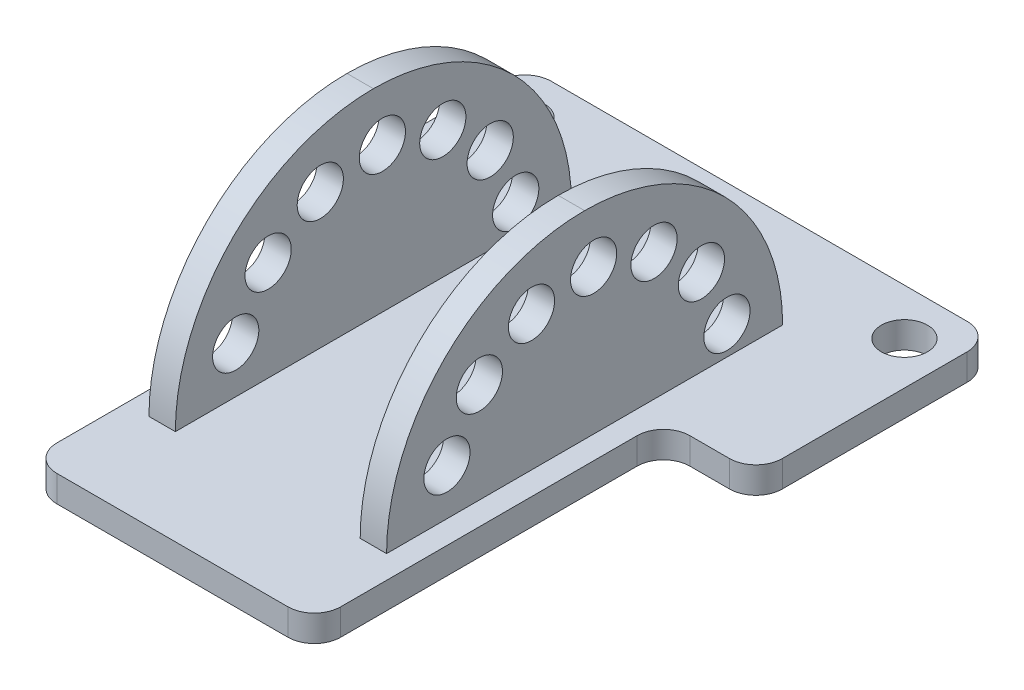
SolidWorks part; units mm, degrees
ref_plane "Front Plane" through (0, 0, 0) normal (0, 0, 1) x (1, 0, 0)
ref_plane "Top Plane" through (0, 0, 0) normal (0, 1, 0) x (1, 0, 0)
ref_plane "Right Plane" through (0, 0, 0) normal (1, 0, 0) x (0, 0, -1)
sketch "Sketch1" plane through (0, 0, 0) normal (0, 1, 0) x (1, 0, 0)
  line L1 (-17.75, 22.225) -> (17.75, 22.225)
  line L2 (-17.75, 22.225) -> (-17.75, -22.225)
  line L3 (-17.75, -22.225) -> (17.75, -22.225)
  line L4 (17.75, 22.225) -> (17.75, -22.225)
  line L5 (-17.75, 22.225) -> (17.75, -22.225) construction
  line L6 (-17.75, -22.225) -> (17.75, 22.225) construction
  point P0 (0, 0)
  dimension "D1" = 35.5
  dimension "D2" = 44.45
extrude "Boss-Extrude1" add sketch "Sketch1" along normal blind 2
sketch "Sketch2" plane through (0, 2, 0) normal (0, 1, 0) x (1, 0, 0)
  line L0 (17.75, 22.225) -> (-17.75, 22.225) construction
  circle A0 centre (-14.5, 18.725) radius 1.75
  circle A1 centre (14.5, 18.725) radius 1.75
  point P4 (0, 22.225)
  dimension "D3" = 3.5
  dimension "D4" = 3.5
  dimension "D1" = 14.5
  dimension "D2" = 14.5
  dimension "D5" = 3.5
  dimension "D6" = 3.5
extrude "Cut-Extrude1" cut sketch "Sketch2" against normal through all
sketch "Sketch3" plane through (0, 2, 0) normal (0, 1, 0) x (1, 0, 0)
  line L0 (-17.75, 22.225) -> (-17.75, -22.225) construction
  line L1 (-17.75, 4.225) -> (-10.75, 4.225)
  line L2 (-17.75, 4.225) -> (-17.75, -22.225)
  line L3 (-17.75, -22.225) -> (-10.75, -22.225)
  line L4 (-10.75, 4.225) -> (-10.75, -22.225)
  line L5 (-17.75, -22.225) -> (17.75, -22.225) construction
  line L6 (17.75, -22.225) -> (17.75, 22.225) construction
  line L7 (17.75, 4.225) -> (10.75, 4.225)
  line L8 (17.75, 4.225) -> (17.75, -22.225)
  line L9 (17.75, -22.225) -> (10.75, -22.225)
  line L10 (10.75, 4.225) -> (10.75, -22.225)
  line L11 (17.75, 22.225) -> (-17.75, 22.225) construction
  dimension "D1" = 7
  dimension "D2" = 7
  dimension "D3" = 18
  dimension "D4" = 18
extrude "Cut-Extrude2" cut sketch "Sketch3" against normal through all
fillet "Fillet1" radius 2 8 edges at (-10.75, 1, -4.225) (-17.75, 1, -4.225) (-10.75, 1, 22.225) (10.75, 1, 22.225) (10.75, 1, -4.225) (17.75, 1, -4.225) (17.75, 1, -22.225) (-17.75, 1, -22.225)
sketch "Sketch4" plane through (0, 2, 0) normal (0, 1, 0) x (1, 0, 0)
  line L1 (-9, 15) -> (-7, 15)
  line L2 (-9, 15) -> (-9, -15)
  line L3 (-9, -15) -> (-7, -15)
  line L4 (-7, 15) -> (-7, -15)
  dimension "D1" = 15
  dimension "D2" = 30
  dimension "D3" = 2
  dimension "D4" = 7
extrude "Boss-Extrude3" add sketch "Sketch4" along normal blind 15
fillet "Fillet2" radius 15 2 edges at (-8, 17, 15) (-8, 17, -15)
sketch "Sketch5" plane through (-9, 0, 0) normal (-1, 0, 0) x (0, 0, 1)
  line L1 (-15, 2) -> (15, 2) construction
  circle A0 centre (10.4283, 5.5) radius 1.75
  arc A1 (15, 2) -> (0, 17) centre (0, 2) ccw construction
  dimension "D3" = 3.5
  dimension "D1" = 3.5
  dimension "D2" = 11
extrude "Cut-Extrude3" cut sketch "Sketch5" against normal through all
pattern_circular "CirPattern1" count 7 every 25 about axis through (-9, 2, 0) along (-1, 0, 0) of "Cut-Extrude3"
mirror "Mirror1" about plane through (0, 0, 0) normal (1, 0, 0) of "CirPattern1", "Cut-Extrude3", "Fillet2", "Boss-Extrude3"
